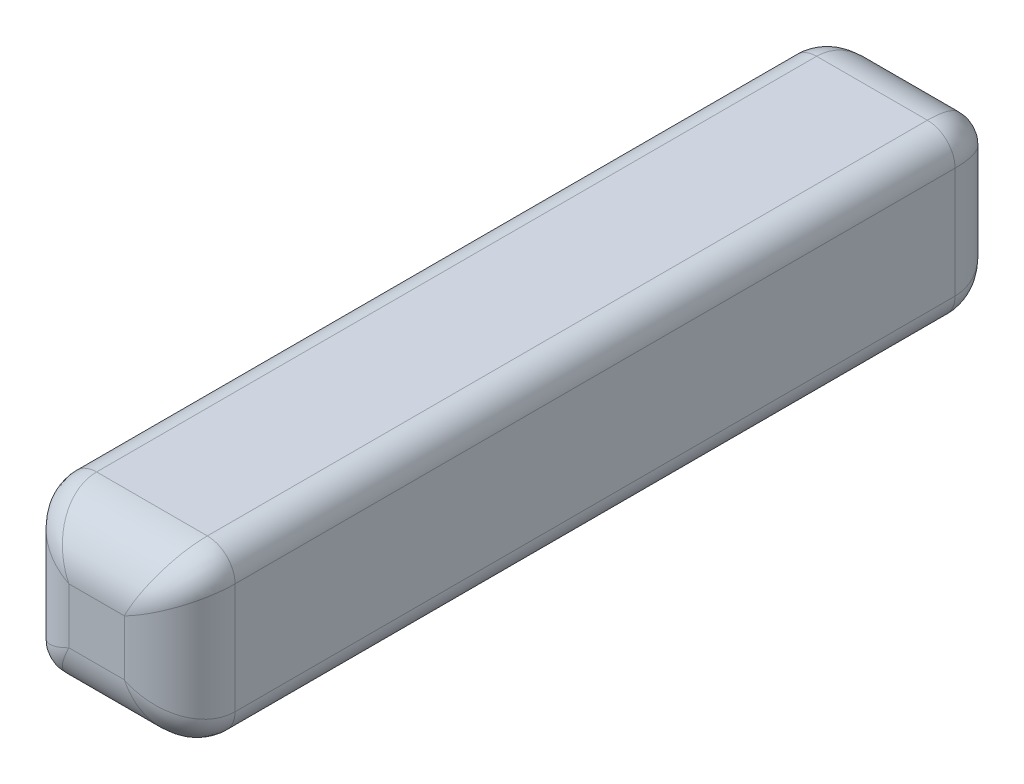
SolidWorks part; units mm, degrees
material "ABS"
ref_plane "前视基准面" through (0, 0, 0) normal (0, 0, 1) x (1, 0, 0)
ref_plane "上视基准面" through (0, 0, 0) normal (0, 1, 0) x (1, 0, 0)
ref_plane "右视基准面" through (0, 0, 0) normal (1, 0, 0) x (0, 0, -1)
sketch "草图1" plane through (0, 0, 0) normal (0, 0, 1) x (1, 0, 0)
  line L1 (-1.5, -1.5) -> (1.5, -1.5)
  line L2 (-1.5, -1.5) -> (-1.5, 1.5)
  line L3 (-1.5, 1.5) -> (1.5, 1.5)
  line L4 (1.5, -1.5) -> (1.5, 1.5)
  line L5 (-1.5, -1.5) -> (1.5, 1.5) construction
  line L6 (-1.5, 1.5) -> (1.5, -1.5) construction
  point P0 (0, 0)
  dimension "D1" = 3
  dimension "D2" = 3
extrude "凸台-拉伸1" add sketch "草图1" along normal blind 15
fillet "圆角1" radius 1 8 edges at (0, 1.5, 0) (-1.5, 0, 0) (0, -1.5, 0) (1.5, 0, 0) (0, 1.5, 15) (1.5, 0, 15) (0, -1.5, 15) (-1.5, 0, 15)
fillet "圆角2" radius 0.5 12 edges at (1.2071, 1.2071, 14.7071) (1.2071, 1.2071, 0.2929) (1.2071, -1.2071, 14.7071) (1.2071, -1.2071, 0.2929) (-1.2071, -1.2071, 14.7071) (-1.2071, -1.2071, 0.2929) (-1.2071, 1.2071, 14.7071) (-1.2071, 1.2071, 0.2929) (1.5, 1.5, 7.5) (1.5, -1.5, 7.5) (-1.5, -1.5, 7.5) (-1.5, 1.5, 7.5)
